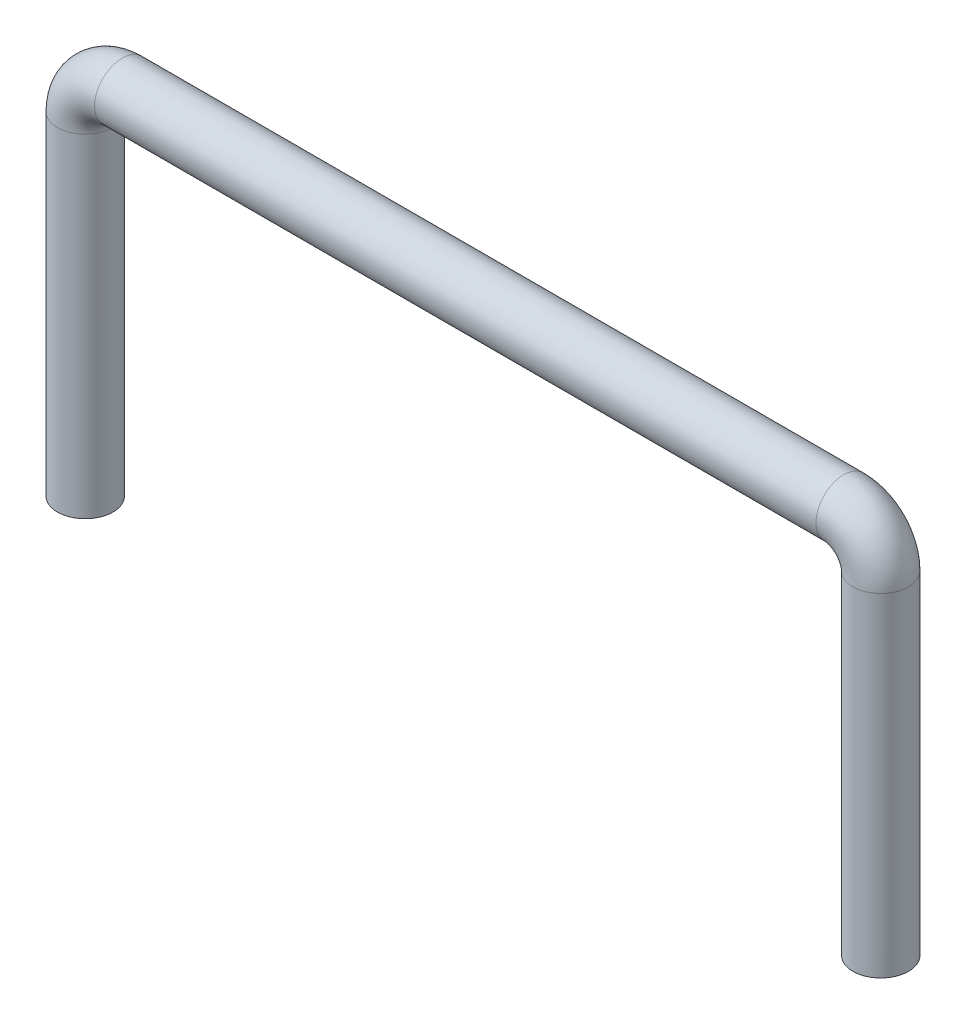
SolidWorks part; units mm, degrees
ref_plane "Front Plane" through (0, 0, 0) normal (0, 0, 1) x (1, 0, 0)
ref_plane "Top Plane" through (0, 0, 0) normal (0, 1, 0) x (1, 0, 0)
ref_plane "Right Plane" through (0, 0, 0) normal (1, 0, 0) x (0, 0, -1)
sketch "Sketch1" plane through (0, 0, 0) normal (0, 0, 1) x (1, 0, 0)
  line L1 (-130.4161, 0) -> (-130.4161, 90)
  line L2 (-120.4161, 100) -> (74.5839, 100)
  line L3 (84.5839, 90) -> (84.5839, 0)
  arc A0 (74.5839, 100) -> (84.5839, 90) centre (74.5839, 90) cw
  arc A1 (-130.4161, 90) -> (-120.4161, 100) centre (-120.4161, 90) cw
  point P4 (84.5839, 100)
  point P9 (-130.4161, 100)
  dimension "D3" = 10
  dimension "D1" = 100
  dimension "D2" = 215
sketch "Sketch2" plane through (0, 0, 0) normal (0, 1, 0) x (1, 0, 0)
  circle A0 centre (-130.4161, 0) radius 7.5
  dimension "D1" = 15
sweep "Sweep1" add profiles "Sketch2" path "Sketch1"
